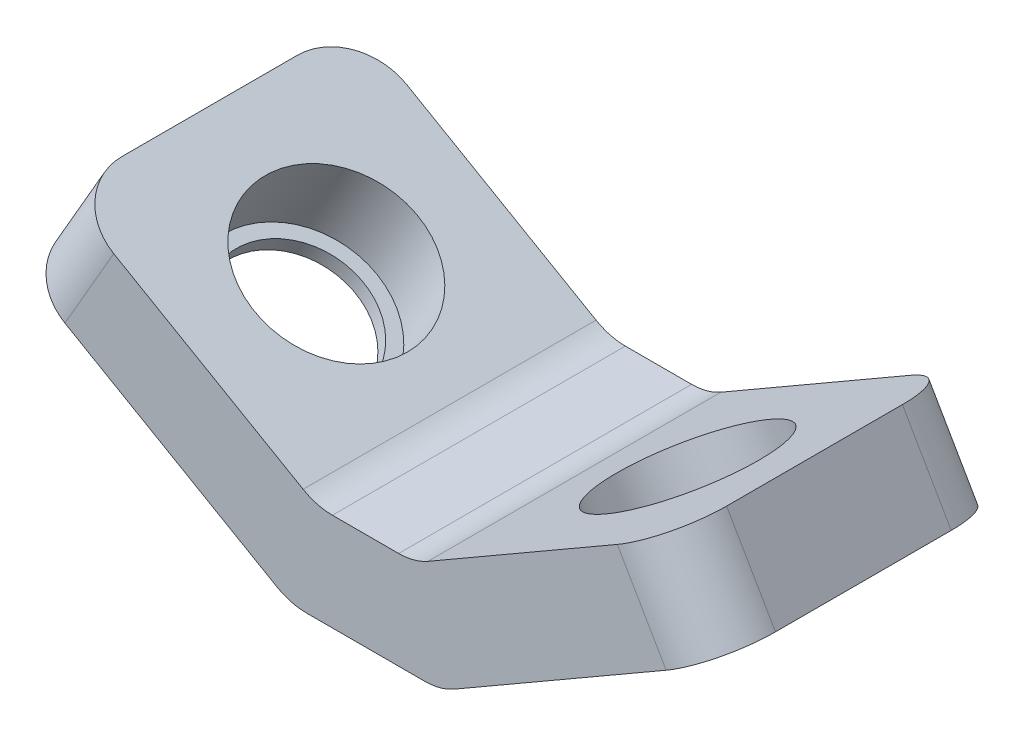
SolidWorks part; units mm, degrees
ref_plane "正面" through (0, 0, 0) normal (0, 0, 1) x (1, 0, 0)
ref_plane "平面" through (0, 0, 0) normal (0, 1, 0) x (1, 0, 0)
ref_plane "右側面" through (0, 0, 0) normal (1, 0, 0) x (0, 0, -1)
sketch "ｽｹｯﾁ1" plane through (0, 0, 0) normal (0, 0, 1) x (1, 0, 0)
  line L0 (0, 0) -> (-14.1506, 8.1699)
  line L1 (-14.1506, 8.1699) -> (-11.6506, 12.5)
  line L2 (-11.6506, 12.5) -> (1.3397, 5)
  line L3 (1.3397, 5) -> (6.3397, 5)
  line L4 (6.3397, 5) -> (19.3301, 12.5)
  line L5 (19.3301, 12.5) -> (21.8301, 8.1699)
  line L6 (21.8301, 8.1699) -> (7.6795, 0)
  line L7 (7.6795, 0) -> (0, 0)
  dimension "D1" = 150
  dimension "D2" = 150
  dimension "D3" = 5
  dimension "D4" = 5
  dimension "D5" = 5
  dimension "D6" = 15
  dimension "D7" = 15
  dimension "D8" = 5
extrude "ﾎﾞｽ - 押し出し1" add sketch "ｽｹｯﾁ1" along normal mid plane 15
sketch "ｽｹｯﾁ2" plane through (0, 0, 0) normal (-0.5, -0.866, 0) x (0, 0, 1)
  line L0 (7.5, 1.3397) -> (7.5, 16.3397) construction
  circle A0 centre (0, 8.8397) radius 4.2
  point P6 (7.5, 8.8397)
  dimension "D1" = 8.4
extrude "ｶｯﾄ - 押し出し1" cut sketch "ｽｹｯﾁ2" against normal through all both and the other way through all
sketch "ｽｹｯﾁ3" plane through (1.9199, -3.3253, 0) normal (0.5, -0.866, 0) x (0, 0, -1)
  line L0 (-7.5, 22.9904) -> (-7.5, 7.9904) construction
  line L1 (-7.5, 22.9904) -> (7.5, 22.9904) construction
  circle A0 centre (0, 15.4904) radius 4.2
  point P4 (-7.5, 15.4904)
  point P7 (0, 22.9904)
  dimension "D1" = 8.4
extrude "ｶｯﾄ - 押し出し2" cut sketch "ｽｹｯﾁ3" against normal through all both and the other way through all
fillet "ﾌｨﾚｯﾄ1" radius 3 8 edges at (20.5801, 10.3349, -7.5) (20.5801, 10.3349, 7.5) (-12.9006, 10.3349, -7.5) (-12.9006, 10.3349, 7.5) (7.6795, 0, 0) (0, 0, 0) (6.3397, 5, 0) (1.3397, 5, 0)
sketch "ｽｹｯﾁ4" plane through (0, 0, 0) normal (0.5, 0.866, 0) x (0.866, -0.5, 0)
  circle A0 centre (-8.8397, 0) radius 4.2 construction
  circle A1 centre (-8.8397, 0) radius 4.2
  circle A2 centre (-8.8397, 0) radius 3.5
  dimension "D1" = 7
extrude "ﾎﾞｽ - 押し出し2" add sketch "ｽｹｯﾁ4" along normal blind 0.8
sketch "ｽｹｯﾁ5" plane through (1.9199, -3.3253, 0) normal (-0.5, 0.866, 0) x (0.866, 0.5, 0)
  circle A0 centre (15.4904, 0) radius 4.2 construction
  circle A1 centre (15.4904, 0) radius 4.2
  circle A2 centre (15.4904, 0) radius 3.5
  dimension "D1" = 7
extrude "ﾎﾞｽ - 押し出し3" add sketch "ｽｹｯﾁ5" along normal blind 0.8
equation "\"D4@ｽｹｯﾁ1\"=\"D3@ｽｹｯﾁ1\""
equation "\"D5@ｽｹｯﾁ1\"=\"D3@ｽｹｯﾁ1\""
equation "\"D2@ｽｹｯﾁ1\"=\"D1@ｽｹｯﾁ1\""
